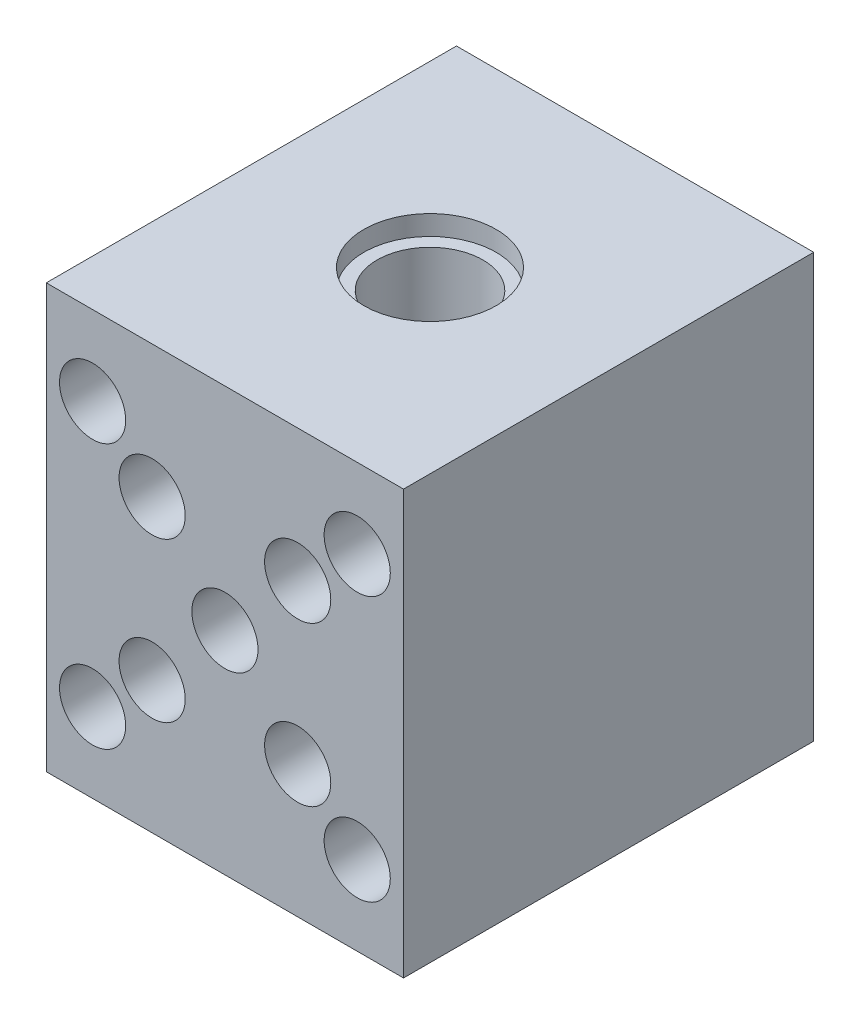
SolidWorks part; units mm, degrees
ref_plane "Piano frontale" through (0, 0, 0) normal (0, 0, 1) x (1, 0, 0)
ref_plane "Piano superiore" through (0, 0, 0) normal (0, 1, 0) x (1, 0, 0)
ref_plane "Piano destro" through (0, 0, 0) normal (1, 0, 0) x (0, 0, -1)
sketch "Schizzo1" plane through (0, 0, 0) normal (0, 0, 1) x (1, 0, 0)
  line L1 (-13.5, 16) -> (13.5, 16)
  line L2 (-13.5, 16) -> (-13.5, -16)
  line L3 (-13.5, -16) -> (13.5, -16)
  line L4 (13.5, 16) -> (13.5, -16)
  line L5 (-13.5, 16) -> (13.5, -16) construction
  line L6 (-13.5, -16) -> (13.5, 16) construction
  point P0 (0, 0)
  dimension "D1" = 27
  dimension "D2" = 32
extrude "Estrusione-Estrusione1" add sketch "Schizzo1" along normal blind 31
sketch "Schizzo2" plane through (0, 0, 0) normal (0, 0, -1) x (-1, 0, 0)
  line L1 (-10, 10) -> (10, 10) construction
  line L2 (-10, 10) -> (-10, -10) construction
  line L3 (-10, -10) -> (10, -10) construction
  line L4 (10, 10) -> (10, -10) construction
  line L5 (-10, 10) -> (10, -10) construction
  line L6 (-10, -10) -> (10, 10) construction
  circle A0 centre (-10, 10) radius 1.5
  circle A1 centre (10, 10) radius 1.5
  circle A2 centre (10, -10) radius 1.5
  circle A3 centre (-10, -10) radius 1.5
  point P0 (0, 0)
  dimension "D3" = 3
  dimension "D1" = 20
  dimension "D2" = 20
extrude "Taglio-Estrusione1" cut sketch "Schizzo2" against normal through all
sketch "Schizzo3" plane through (0, 16, 0) normal (0, 1, 0) x (1, 0, 0)
  circle A0 centre (0, -15.5) radius 4
  dimension "D1" = 8
extrude "Taglio-Estrusione2" cut sketch "Schizzo3" against normal through all
sketch "Schizzo4" plane through (0, 16, 0) normal (0, 1, 0) x (1, 0, 0)
  circle A0 centre (0, -15.5) radius 5
  circle A1 centre (0, -15.5) radius 4 construction
  dimension "D1" = 10
extrude "Taglio-Estrusione5" cut sketch "Schizzo4" against normal blind 1.5
sketch "Schizzo5" plane through (0, -16, 0) normal (0, -1, 0) x (1, 0, 0)
  circle A0 centre (0, 15.5) radius 5
  circle A1 centre (0, 15.5) radius 4 construction
  dimension "D1" = 10
extrude "Taglio-Estrusione6" cut sketch "Schizzo5" against normal blind 1.5
sketch "Schizzo6" plane through (0, 0, 31) normal (0, 0, 1) x (1, 0, 0)
  line L1 (-10, 10) -> (10, 10) construction
  line L2 (-10, 10) -> (-10, -10) construction
  line L3 (-10, -10) -> (10, -10) construction
  line L4 (10, 10) -> (10, -10) construction
  line L5 (-10, 10) -> (10, -10) construction
  line L6 (-10, -10) -> (10, 10) construction
  circle A0 centre (-10, 10) radius 2.5
  circle A1 centre (10, 10) radius 2.5
  circle A2 centre (10, -10) radius 2.5
  circle A3 centre (-10, -10) radius 2.5
  point P0 (0, 0)
  dimension "D1" = 5
extrude "Taglio-Estrusione7" cut sketch "Schizzo6" against normal blind 15
sketch "Schizzo7" plane through (0, 0, 31) normal (0, 0, 1) x (1, 0, 0)
  line L0 (-13.5, 16) -> (-13.5, -16) construction
  line L1 (-5.5, 6) -> (5.5, 6) construction
  line L2 (-5.5, 6) -> (-5.5, -6) construction
  line L3 (-5.5, -6) -> (5.5, -6) construction
  line L4 (5.5, 6) -> (5.5, -6) construction
  line L5 (-5.5, 6) -> (5.5, -6) construction
  line L6 (-5.5, -6) -> (5.5, 6) construction
  line L9 (-13.5, -16) -> (13.5, -16) construction
  circle A0 centre (-5.5, 6) radius 2.5
  circle A1 centre (5.5, 6) radius 2.5
  circle A2 centre (0, 0) radius 2.5
  circle A3 centre (5.5, -6) radius 2.5
  circle A4 centre (-5.5, -6) radius 2.5
  point P0 (0, 0)
  dimension "D3" = 5
  dimension "D1" = 8
  dimension "D2" = 10
extrude "Taglio-Estrusione8" cut sketch "Schizzo7" against normal blind 10
